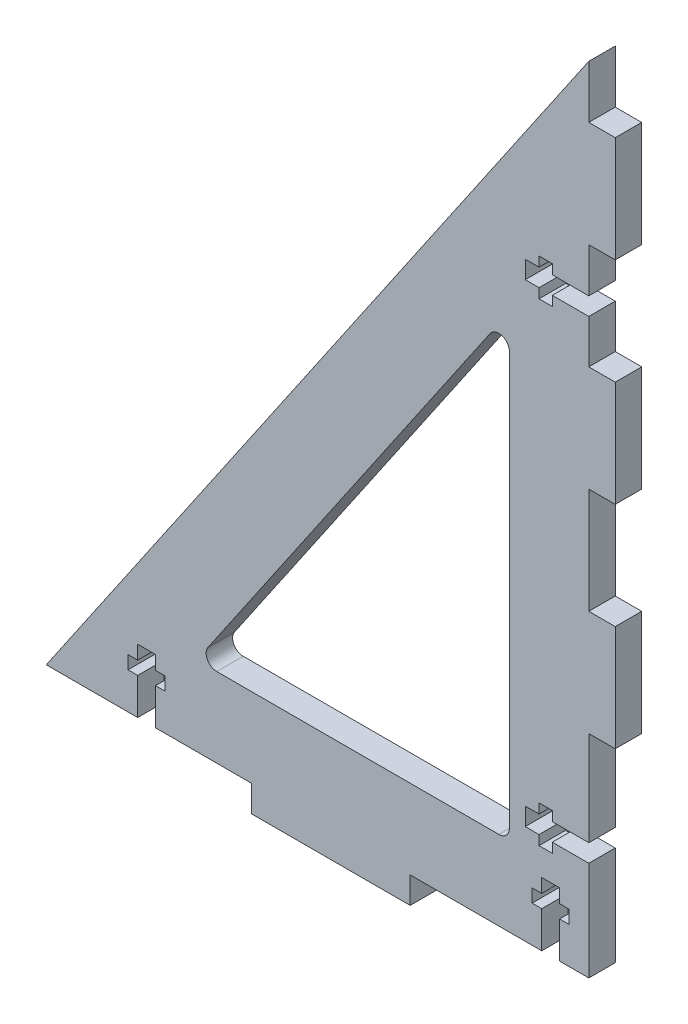
SolidWorks part; units mm, degrees
ref_plane "Front Plane" through (0, 0, 0) normal (0, 0, 1) x (1, 0, 0)
ref_plane "Top Plane" through (0, 0, 0) normal (0, 1, 0) x (1, 0, 0)
ref_plane "Right Plane" through (0, 0, 0) normal (1, 0, 0) x (0, 0, -1)
sketch "Sketch1" plane through (0, 0, 0) normal (0, 0, 1) x (1, 0, 0)
  line L0 (69.85, 285.75) -> (69.85, 95.25)
  line L1 (69.85, 171.45) -> (69.85, 222.25) construction
  line L2 (69.85, 95.25) -> (-60.325, 95.25)
  line L3 (-60.325, 95.25) -> (69.85, 285.75)
  dimension "D1" = 190.5
  dimension "D2" = 130.175
extrude "Boss-Extrude1" add sketch "Sketch1" along normal mid plane 6.35
sketch "Sketch2" plane through (0, 0, 3.175) normal (0, 0, 1) x (1, 0, 0)
  line L9 (-24.2346, 114.3) -> (50.8, 114.3)
  line L10 (50.8, 114.3) -> (50.8, 224.1068)
  line L11 (50.8, 224.1068) -> (-24.2346, 114.3)
  line L12 (-24.2346, 114.3) -> (50.8, 114.3)
  line L13 (50.8, 114.3) -> (50.8, 224.1068)
  line L14 (50.8, 224.1068) -> (-24.2346, 114.3)
  dimension "D1" = 19.05
extrude "Cut-Extrude1" cut sketch "Sketch2" against normal through all
sketch "Sketch3" plane through (0, 0, -3.175) normal (0, 0, -1) x (-1, 0, 0)
  line L0 (-64.5407, 95.25) -> (-36.8762, 95.25) construction
  line L1 (60.325, 95.25) -> (-69.85, 95.25) construction
  line L2 (-69.85, 463.55) -> (-69.85, 6.35) construction
  line L3 (-69.85, 121.2302) -> (-54.61, 121.2302) construction
  line L4 (36.2599, 95.25) -> (36.2599, 110.49) construction
  line L5 (-60.6943, 95.25) -> (-60.6943, 110.49) construction
  line L8 (-69.85, 234.867) -> (-54.61, 234.867) construction
  line B0 (-62.8279, 95.25) -> (-58.5607, 95.25)
  line B1 (-58.5607, 107.188) -> (-56.2493, 107.188)
  line B2 (-56.2493, 107.188) -> (-56.2493, 104.013)
  line B3 (-56.2493, 104.013) -> (-58.5607, 104.013)
  line B4 (-58.5607, 104.013) -> (-58.5607, 95.25)
  line B5 (-58.5607, 107.188) -> (-58.5607, 110.49)
  line B6 (-58.5607, 110.49) -> (-62.8279, 110.49)
  line B7 (-62.8279, 107.188) -> (-62.8279, 110.49)
  line B8 (-62.8279, 104.013) -> (-62.8279, 95.25)
  line B9 (-65.1393, 104.013) -> (-62.8279, 104.013)
  line B10 (-65.1393, 107.188) -> (-65.1393, 104.013)
  line B11 (-62.8279, 107.188) -> (-65.1393, 107.188)
  line B12 (34.1263, 95.25) -> (38.3935, 95.25)
  line B13 (38.3935, 107.188) -> (40.7049, 107.188)
  line B14 (40.7049, 107.188) -> (40.7049, 104.013)
  line B15 (40.7049, 104.013) -> (38.3935, 104.013)
  line B16 (38.3935, 104.013) -> (38.3935, 95.25)
  line B17 (38.3935, 107.188) -> (38.3935, 110.49)
  line B18 (38.3935, 110.49) -> (34.1263, 110.49)
  line B19 (34.1263, 107.188) -> (34.1263, 110.49)
  line B20 (34.1263, 104.013) -> (34.1263, 95.25)
  line B21 (31.8149, 104.013) -> (34.1263, 104.013)
  line B22 (31.8149, 107.188) -> (31.8149, 104.013)
  line B23 (34.1263, 107.188) -> (31.8149, 107.188)
  line B24 (-69.85, 237.0006) -> (-69.85, 232.7334)
  line B25 (-57.912, 232.7334) -> (-57.912, 230.422)
  line B26 (-57.912, 230.422) -> (-61.087, 230.422)
  line B27 (-61.087, 230.422) -> (-61.087, 232.7334)
  line B28 (-61.087, 232.7334) -> (-69.85, 232.7334)
  line B29 (-57.912, 232.7334) -> (-54.61, 232.7334)
  line B30 (-54.61, 232.7334) -> (-54.61, 237.0006)
  line B31 (-57.912, 237.0006) -> (-54.61, 237.0006)
  line B32 (-61.087, 237.0006) -> (-69.85, 237.0006)
  line B33 (-61.087, 239.312) -> (-61.087, 237.0006)
  line B34 (-57.912, 239.312) -> (-61.087, 239.312)
  line B35 (-57.912, 237.0006) -> (-57.912, 239.312)
  line B36 (-69.85, 123.3638) -> (-69.85, 119.0966)
  line B37 (-57.912, 119.0966) -> (-57.912, 116.7852)
  line B38 (-57.912, 116.7852) -> (-61.087, 116.7852)
  line B39 (-61.087, 116.7852) -> (-61.087, 119.0966)
  line B40 (-61.087, 119.0966) -> (-69.85, 119.0966)
  line B41 (-57.912, 119.0966) -> (-54.61, 119.0966)
  line B42 (-54.61, 119.0966) -> (-54.61, 123.3638)
  line B43 (-57.912, 123.3638) -> (-54.61, 123.3638)
  line B44 (-61.087, 123.3638) -> (-69.85, 123.3638)
  line B45 (-61.087, 125.6752) -> (-61.087, 123.3638)
  line B46 (-57.912, 125.6752) -> (-61.087, 125.6752)
  line B47 (-57.912, 123.3638) -> (-57.912, 125.6752)
sketch_block_instance "TSlot-1"
sketch_block "TSlot" parameters "D1"=3.302, "D2"=3.175
sketch_block_instance "TSlot-3"
sketch_block_instance "TSlot-4"
sketch_block_instance "TSlot-5"
extrude "Cut-Extrude2" cut sketch "Sketch3" against normal blind 6.35
sketch "Sketch4" plane through (69.85, 0, 0) normal (1, 0, 0) x (0, 0, -1)
  line L0 (-3.175, 237.0006) -> (-3.175, 285.75) construction
  line L1 (-3.175, 273.05) -> (3.175, 273.05)
  line L2 (-3.175, 273.05) -> (-3.175, 247.65)
  line L3 (-3.175, 247.65) -> (3.175, 247.65)
  line L4 (3.175, 273.05) -> (3.175, 247.65)
  line L5 (3.175, 237.0006) -> (3.175, 285.75) construction
  dimension "D1" = 25.4
  dimension "D2" = 12.7
extrude "Boss-Extrude2" add sketch "Sketch4" along normal blind 6.35
pattern_linear "LPattern1" count 3 spacing 50.8 along (0, -1, 0) of "Boss-Extrude2"
fillet "Fillet1" radius 2.54 3 edges at (50.8, 224.1068, 0) (50.8, 114.3, 0) (-24.2346, 114.3, 0)
sketch "Sketch5" plane through (0, 95.25, 0) normal (0, -1, 0) x (-1, 0, 0)
  line L0 (34.1263, -3.175) -> (-58.5607, -3.175) construction
  line L1 (11.1125, -3.175) -> (-26.9875, -3.175)
  line L2 (11.1125, -3.175) -> (11.1125, 3.175)
  line L3 (11.1125, 3.175) -> (-26.9875, 3.175)
  line L4 (-26.9875, -3.175) -> (-26.9875, 3.175)
  line L5 (34.1263, 3.175) -> (-58.5607, 3.175) construction
  line L6 (-7.9375, -27.772) -> (-7.9375, 19.1203) construction
  line L7 (60.325, -3.175) -> (60.325, 3.175) construction
  line L8 (-76.2, -3.175) -> (-76.2, 3.175) construction
  dimension "D1" = 38.1
extrude "Boss-Extrude3" add sketch "Sketch5" along normal blind 6.35
